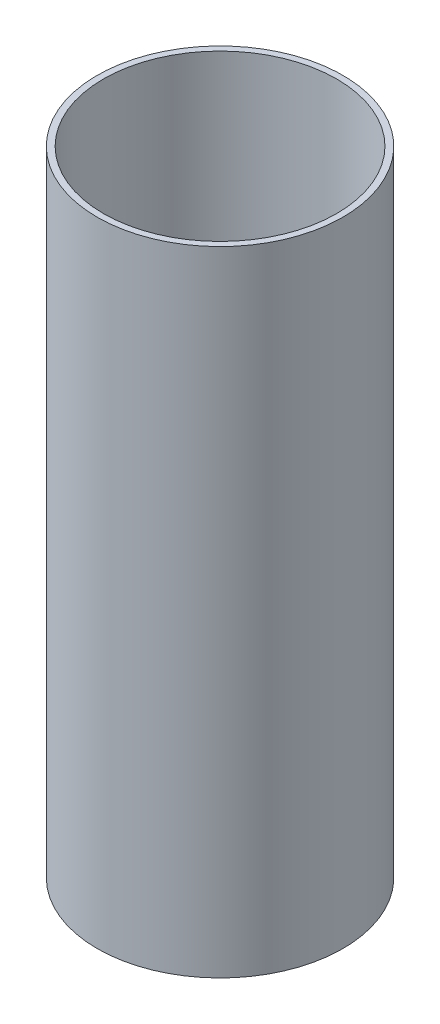
SolidWorks part; units mm, degrees
material "PVC Rigid"
ref_plane "Front Plane" through (0, 0, 0) normal (0, 0, 1) x (1, 0, 0)
ref_plane "Top Plane" through (0, 0, 0) normal (0, 1, 0) x (1, 0, 0)
ref_plane "Right Plane" through (0, 0, 0) normal (1, 0, 0) x (0, 0, -1)
sketch "Sketch1" plane through (0, 0, 0) normal (0, 1, 0) x (1, 0, 0)
  circle A0 centre (0, 0) radius 93.6625
  circle A1 centre (0, 0) radius 88.9
  dimension "D1" = 187.325
  dimension "D2" = 177.8
extrude "Boss-Extrude1" add sketch "Sketch1" along normal mid plane 482.854
ref_plane "Plane1" through (0, 0, 93.6625) normal (0, 0, 1) x (1, 0, 0)
sketch "Sketch3" plane through (0, 0, 93.6625) normal (0, 0, 1) x (1, 0, 0)
  line L0 (0, -55) -> (0, 55) construction
  line L1 (-93.6625, -241.427) -> (93.6625, -241.427) construction
  circle A0 centre (0, -235.077) radius 1.4351
  dimension "D1" = 2.8702
  dimension "D2" = 6.35
extrude "Cut-Extrude1" [suppressed] cut sketch "Sketch3" against normal blind 19.304
pattern_circular "CirPattern1" [suppressed] count 12 over 360 reverse direction yes of bodies 102
mirror "Mirror1" [suppressed] about plane through (0, 0, 0) normal (0, 1, 0)
sketch "Sketch4" [suppressed] plane through (0, 0, 93.6625) normal (0, 0, 1) x (1, 0, 0)
  line L0 (0, -103.0288) -> (0, 103.0288) construction
  circle A0 centre (0, -78.359) radius 1.4351
  circle A1 centre (0, 78.359) radius 1.4351
  circle A2 centre (0, 235.077) radius 1.4351 construction
  circle A3 centre (0, -235.077) radius 1.4351 construction
  dimension "D1" = 2.8702
  dimension "D2" = 2.8702
  dimension "D3" = 156.718
  dimension "D4" = 156.718
extrude "Cut-Extrude2" [suppressed] cut sketch "Sketch4" against normal blind 25.146
pattern_circular "CirPattern2" [suppressed] count 3 over 360 of bodies 105
